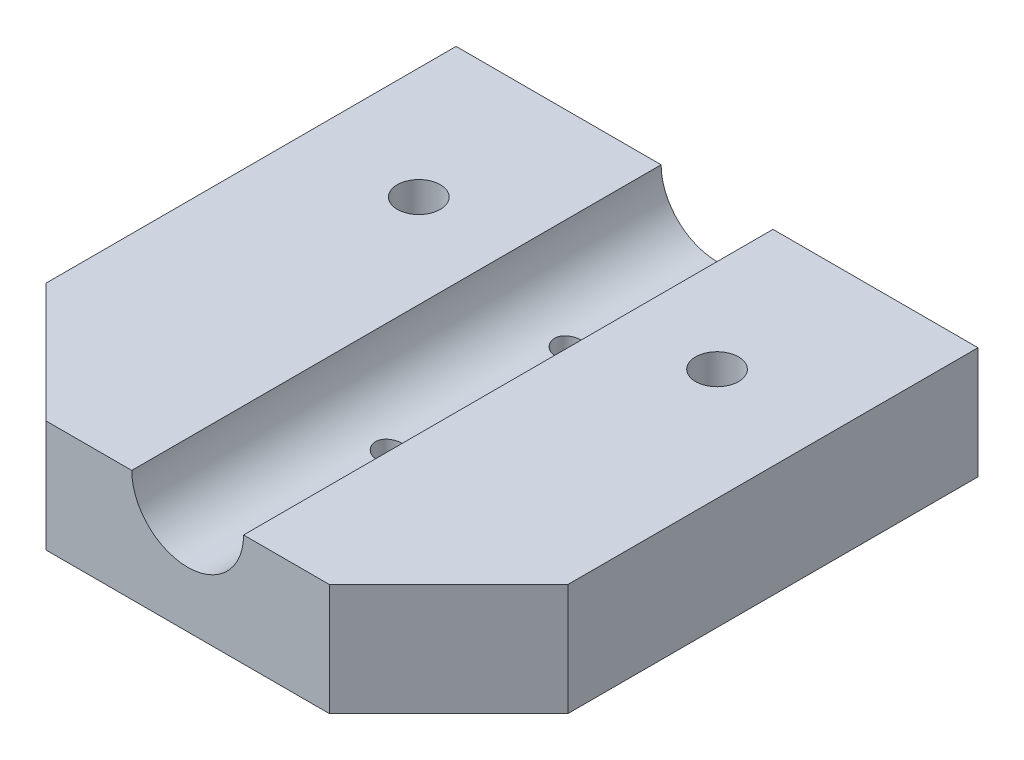
SolidWorks part; units mm, degrees
material "Nylon 6/10"
ref_plane "Front Plane" through (0, 0, 0) normal (0, 0, 1) x (1, 0, 0)
ref_plane "Top Plane" through (0, 0, 0) normal (0, 1, 0) x (1, 0, 0)
ref_plane "Right Plane" through (0, 0, 0) normal (1, 0, 0) x (0, 0, -1)
sketch "Sketch1" plane through (0, 0, 0) normal (0, 1, 0) x (1, 0, 0)
  line L1 (-22.225, -22.5425) -> (22.225, -22.5425)
  line L2 (-22.225, -22.5425) -> (-22.225, 22.5425)
  line L3 (-22.225, 22.5425) -> (22.225, 22.5425)
  line L4 (22.225, -22.5425) -> (22.225, 22.5425)
  line L5 (-22.225, -22.5425) -> (22.225, 22.5425) construction
  line L6 (-22.225, 22.5425) -> (22.225, -22.5425) construction
  point P0 (0, 0)
  dimension "D1" = 45.085
  dimension "D2" = 44.45
extrude "Boss-Extrude1" add sketch "Sketch1" along normal blind 9.525
sketch "Sketch4" plane through (0, 0, 22.5425) normal (0, 0, 1) x (1, 0, 0)
  line L0 (-22.225, 9.525) -> (22.225, 9.525) construction
  circle A0 centre (0, 9.525) radius 4.7625
  dimension "D1" = 9.525
extrude "Cut-Extrude1" cut sketch "Sketch4" against normal through all
hole_wizard "MotorHoles" positions "Sketch3" profile "Sketch2" tap size "#4-40" standard "ANSI Inch"
sketch "Sketch3" plane through (0, 0, 0) normal (0, -1, 0) x (-1, 0, 0)
  line L0 (22.225, -22.5425) -> (-22.225, -22.5425) construction
  line L2 (0, 0) -> (0, -31.1437) construction
  point P0 (-5.715, -19.3675)
  point P2 (5.715, -19.3675)
  point P15 (13.081, 19.6469)
  point P17 (-13.081, 19.6469)
  dimension "D1" = 3.175
  dimension "D2" = 11.43
  dimension "D3" = 39.0144
  dimension "D4" = 7.366
  dimension "D5" = 7.366
cosmetic thread "Hole Thread1" parameters "D1"=5.588, "D2"=2.8448
cosmetic thread "Hole Thread2" parameters "D1"=5.588, "D2"=2.8448
sketch "Sketch2" plane through (5.715, 0, 19.3675) normal (1, 0, 0) x (0, 0, -1)
  line L0 (0, 0) -> (0, 7.0292)
  line L1 (0, 7.0292) -> (1.1303, 6.35)
  line L2 (1.1303, 6.35) -> (1.1303, 0)
  line L5 (1.1303, 0) -> (0, 0)
  line L10 (0, 7.0292) -> (-1.1303, 6.35) construction
  line L11 (0, -6.35) -> (0, 107.95) construction
  dimension "Tap Drill Dia." = 2.2606
  dimension "Tap Drill Depth" = 6.35
  dimension "Drill Angle" = 118
cosmetic thread "Hole Thread5" parameters "D1"=5.588, "D2"=2.8448
cosmetic thread "Hole Thread6" parameters "D1"=5.588, "D2"=2.8448
hole_wizard "CBORE for #6 Socket Head Cap Screw1" positions "Sketch6" profile "Sketch5" counterbore size "#6" standard "ANSI Inch" end condition through all
sketch "Sketch6" plane through (0, 0, 0) normal (0, -1, 0) x (-1, 0, 0)
  line L0 (0, 0) -> (0, 20.3228) construction
  line L2 (-22.225, 22.5425) -> (22.225, 22.5425) construction
  point P0 (-12.7, 9.8425)
  point P2 (12.7, 9.8425)
  dimension "D1" = 25.4
  dimension "D2" = 12.7
sketch "Sketch5" plane through (12.7, 0, -9.8425) normal (1, 0, 0) x (0, 0, -1)
  line L0 (0, 0) -> (0, 9.525)
  line L1 (0, 9.525) -> (1.8288, 9.525)
  line L3 (1.8288, 9.525) -> (1.8288, 3.5052)
  line L4 (1.8288, 3.5052) -> (3.5725, 3.5052)
  line L5 (3.5725, 3.5052) -> (3.5725, 0)
  line L7 (3.5725, 0) -> (0, 0)
  line L11 (0, -6.35) -> (0, 107.95) construction
  dimension "Thru Hole Dia." = 3.6576
  dimension "Thru Hole Depth" = 9.525
  dimension "C'Bore Dia." = 7.145
  dimension "C'Bore Depth" = 3.5052
chamfer "Chamfer1" distance 10.16 angle 45 2 edges at (22.225, 4.7625, 22.5425) (-22.225, 4.7625, 22.5425)
hole_wizard "#4-40 Tapped Hole1" positions "Sketch8" profile "Sketch7" tap size "#4-40" standard "ANSI Inch" end condition through all
sketch "Sketch8" plane through (0, 0, 0) normal (0, -1, 0) x (-1, 0, 0)
  line L0 (0, 0) -> (0, 3.4708) construction
  line L2 (-12.7, 9.8425) -> (12.7, 9.8425) construction
  circle A0 centre (-12.7, 9.8425) radius 1.8288 construction
  circle A1 centre (12.7, 9.8425) radius 1.8288 construction
  circle A2 centre (-12.7, 9.8425) radius 1.8288 construction
  circle A3 centre (12.7, 9.8425) radius 1.8288 construction
  point P0 (0, 9.8425)
  point P2 (0, -5.3975)
  dimension "D1" = 15.24
sketch "Sketch7" plane through (0, 0, -9.8425) normal (1, 0, 0) x (0, 0, -1)
  line L0 (0, 0) -> (0, 9.525)
  line L1 (0, 9.525) -> (1.1303, 9.525)
  line L2 (1.1303, 9.525) -> (1.1303, 0)
  line L5 (1.1303, 0) -> (0, 0)
  line L11 (0, -6.35) -> (0, 107.95) construction
  dimension "Thru Tap Drill Dia." = 2.2606
  dimension "Thru Tap Drill Depth" = 9.525
cosmetic thread "Hole Thread3" parameters "D2"=2.8448
cosmetic thread "Hole Thread4" parameters "D2"=2.8448
chamfer "Chamfer3" [suppressed] distance 5.08 angle 45
